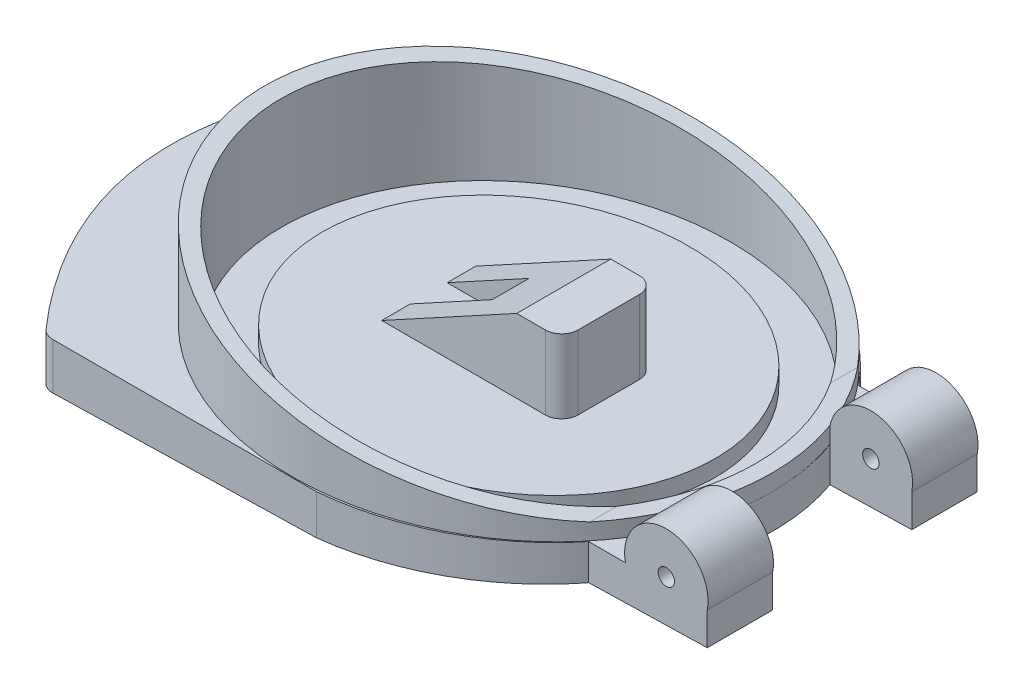
SolidWorks part; units mm, degrees
ref_plane "Front Plane" through (0, 0, 0) normal (0, 0, 1) x (1, 0, 0)
ref_plane "Top Plane" through (0, 0, 0) normal (0, 1, 0) x (1, 0, 0)
ref_plane "Right Plane" through (0, 0, 0) normal (1, 0, 0) x (0, 0, -1)
sketch "Sketch8" plane through (0, 0, 0) normal (0, 1, 0) x (1, 0, 0)
  line L0 (-55, 0) -> (55, 0) construction
  line L1 (29.5371, 8.5) -> (39.5371, 8.5)
  line L2 (3.1424, -27.8558) -> (-30, -27.8558)
  line L4 (3.1424, 27.8558) -> (-30, 27.8558)
  line L6 (21.6155, -20.0705) -> (-30, 27.8558) construction
  line L7 (21.6155, 20.0705) -> (-30, -27.8558) construction
  line L8 (29.5371, -8.5) -> (39.5371, -8.5)
  line L9 (39.5371, 8.5) -> (39.5371, 16.5)
  line L10 (39.5371, 16.5) -> (25.0457, 16.5)
  line L11 (39.5371, -8.5) -> (39.5371, -16.5)
  line L12 (39.5371, -16.5) -> (25.0457, -16.5)
  ellipse E0 centre (0, 0) end of major axis (31, 0) minor radius 28
  spline S0 degree 2 poles (-30, 27.8558) (-55, 0) (-30, -27.8558) knots 0 0 0 1 1 1
  dimension "D1" = 62
  dimension "D2" = 28
  dimension "D3" = 17
  dimension "D4" = 8.5
  dimension "D5" = 10
  dimension "D6" = 10
  dimension "D7" = 8
  dimension "D8" = 8
  dimension "D9" = 11.5
extrude "Boss-Extrude5" add sketch "Sketch8" along normal blind 4 contours L4 S0 L2 E0 | E0 L4 L2 | E0 L12 L11 L8 | E0 L1 L9 L10 region at (33.4938, 0, -12.749) region at (0, 0, 0) region at (33.4938, 0, 12.749) region at (-31.6821, 0, 0)
sketch "Sketch9" plane through (0, 4, 0) normal (0, 1, 0) x (1, 0, 0)
  line L0 (-11.457, 0) -> (11.457, 0) construction
  ellipse E0 centre (0, 0) end of major axis (31, 0) minor radius 27.7622
  ellipse E1 centre (0, 0) end of major axis (31, 0) minor radius 28 (29.5371, -8.5) -> (29.5371, 8.5) ccw construction
  ellipse E2 centre (0, 0) end of major axis (29, 0) minor radius 25.886
  dimension "D1" = 2
extrude "Boss-Extrude6" add sketch "Sketch9" along normal blind 12
sketch "Sketch10" plane through (0, 0, 27.8558) normal (0, 0, 1) x (1, 0, 0)
  line L0 (31, 6) -> (25.0457, 6)
  line L1 (31, 4) -> (31, 16) construction
  line L2 (39.5371, 4) -> (25.0457, 4) construction
  line L3 (25.0457, 6) -> (-31, 16)
  line L4 (-31, 16) -> (-31, 18.8124)
  line L5 (-31, 18.8124) -> (31, 18.8124)
  line L6 (31, 18.8124) -> (31, 6)
  dimension "D1" = 2
extrude "Cut-Extrude3" cut sketch "Sketch10" against normal blind 71
sketch "Sketch11" plane through (0, 0, 16.5) normal (0, 0, 1) x (1, 0, 0)
  line L0 (39.5371, 4) -> (39.5371, 5)
  line L1 (39.5371, 5) -> (34.5371, 5)
  line L2 (34.5371, 5) -> (34.5371, 0)
  line L3 (30.6413, 0) -> (-30.6413, 0) construction
  circle A1 centre (34.5371, 5) radius 1
  circle A2 centre (34.5371, 5) radius 5.099
  line M3 (25.0457, 0) -> (39.5371, 0)
  line M5 (39.5371, 4) -> (25.0457, 4)
  dimension "D1" = 5
  dimension "D2" = 5
extrude "Boss-Extrude8" add sketch "Sketch11" against normal up to surface (8 mm away) contours L0 A2 A1 L1 M5 | A1 L0 L1 M5 | A2 L2 M3 M5 | A2 L2 M5 M3 region at (37.4239, 4.4859, 16.5) region at (34.2581, 6.9603, 16.5) region at (36.5866, 2.2964, 16.5) region at (32.4875, 2.2964, 16.5) up to face at (34.5371, 2, 8.5)
sketch "Sketch12" plane through (0, 0, -16.5) normal (0, 0, -1) x (-1, 0, 0)
  line L0 (-34.5371, 4) -> (-34.5371, 5)
  line L1 (-39.5371, 4) -> (-25.0457, 4) construction
  circle A0 centre (-34.5371, 5) radius 1 construction
  circle A1 centre (-34.5371, 5) radius 1
  circle A2 centre (-34.5371, 5) radius 5.099
  line M1 (-39.5371, 0) -> (-25.0457, 0)
  line M3 (-25.0457, 4) -> (-39.5371, 4)
extrude "Boss-Extrude9" add sketch "Sketch12" against normal up to surface (8 mm away) contours A2 M3 M1 | A2 A1 M3 region at (34.5371, 6.7422, -16.5) region at (34.5371, 2.2964, -16.5) up to face at (34.5371, 2, -8.5)
sketch "Sketch14" plane through (0, 4, 0) normal (0, 1, 0) x (1, 0, 0)
  ellipse E3 centre (0, 0) end of major axis (29, 0) minor radius 25.886
  ellipse E4 centre (0, 0) end of major axis (29, 0) minor radius 25.886
  spline S0 degree 3 poles (-24, 0.3714) (-24, -1.4856) (-23.8193, -2.9396) (-23.3806, -4.72) (-23.2821, -5.0742) (-23.0635, -5.7788) (-22.943, -6.1303) (-22.552, -7.1701) (-22.2532, -7.8422) (-21.584, -9.147) (-21.2135, -9.7796) (-20.6056, -10.6997) (-20.3943, -11.0016) (-19.9542, -11.5958) (-19.7252, -11.8884) (-18.5496, -13.3125) (-17.5036, -14.3406) (-15.7909, -15.7312) (-15.193, -16.171) (-13.964, -16.9902) (-13.3343, -17.3692) (-11.4018, -18.419) (-10.0564, -19.0036) (-7.9549, -19.7126) (-7.2449, -19.9191) (-5.8195, -20.271) (-5.1021, -20.4171) (-2.9361, -20.7681) (-1.4729, -20.8864) (1.4872, -20.8856) (2.9474, -20.7667) (5.8294, -20.2988) (7.2511, -19.9499) (9.3526, -19.2411) (10.0422, -18.9754) (11.3858, -18.3907) (12.0419, -18.0709) (13.9629, -17.0283) (15.1807, -16.223) (16.6153, -15.0627) (16.8986, -14.8221) (17.45, -14.33) (17.7186, -14.0782) (18.5026, -13.306) (18.9967, -12.7684) (20.3912, -11.0865) (21.2052, -9.8737) (22.0573, -8.2267) (22.2187, -7.892) (22.5198, -7.2186) (22.6601, -6.879) (23.0504, -5.8515) (23.2698, -5.1549) (23.6258, -3.738) (23.7624, -3.0178) (23.9019, -1.9188) (23.9375, -1.5479) (23.9858, -0.8077) (23.9984, -0.4387) (24.0056, 1.4015) (23.8337, 2.8575) (23.3973, 4.6574) (23.2986, 5.0169) (23.0815, 5.7245) (22.9629, 6.0738) (22.5777, 7.1084) (22.282, 7.7805) (21.6154, 9.0909) (21.2443, 9.7293) (20.4282, 10.9715) (19.9897, 11.5651) (19.0562, 12.7015) (18.5612, 13.2442) (17.5168, 14.2806) (16.9664, 14.7752) (15.2409, 16.1809) (14.0172, 16.9952) (12.0825, 18.0506) (11.4208, 18.3744) (10.0645, 18.9667) (9.372, 19.2339) (7.2805, 19.9414) (5.8572, 20.2933) (3.6806, 20.6482) (2.947, 20.7375) (1.4697, 20.8567) (0.7334, 20.886) (-1.4683, 20.886) (-2.9269, 20.7694) (-5.1007, 20.4175) (-5.823, 20.2705) (-7.2625, 19.9145) (-7.9707, 19.7076) (-10.0554, 19.0033) (-11.3949, 18.4221) (-13.3251, 17.3745) (-13.9552, 16.9958) (-14.8791, 16.3804) (-15.1839, 16.167) (-15.7794, 15.7289) (-16.0709, 15.5037) (-17.4964, 14.347) (-18.5369, 13.3244) (-19.9367, 11.6339) (-20.3763, 11.0442) (-20.9916, 10.1167) (-21.189, 9.8007) (-21.5632, 9.1631) (-21.7407, 8.8406) (-22.5801, 7.2086) (-23.0999, 5.8426) (-23.6348, 3.6962) (-23.7721, 2.9606) (-23.9086, 1.855) (-23.9428, 1.4854) (-23.9885, 0.7443) (-24, 0.3714) (-24, -1.4856) (-23.8193, -2.9396) knots -0.007812 -0.007812 0 0 0.03125 0.03125 0.039063 0.039063 0.046875 0.046875 0.0625 0.0625 0.078125 0.078125 0.085938 0.085938 0.09375 0.09375 0.125 0.125 0.140625 0.140625 0.15625 0.15625 0.1875 0.1875 0.203125 0.203125 0.21875 0.21875 0.25 0.25 0.28125 0.28125 0.3125 0.3125 0.328125 0.328125 0.34375 0.34375 0.375 0.375 0.382813 0.382813 0.390625 0.390625 0.40625 0.40625 0.4375 0.4375 0.445313 0.445313 0.453125 0.453125 0.46875 0.46875 0.484375 0.484375 0.492188 0.492188 0.5 0.5 0.53125 0.53125 0.539063 0.539063 0.546875 0.546875 0.5625 0.5625 0.578125 0.578125 0.59375 0.59375 0.609375 0.609375 0.625 0.625 0.65625 0.65625 0.671875 0.671875 0.6875 0.6875 0.71875 0.71875 0.734375 0.734375 0.75 0.75 0.78125 0.78125 0.796875 0.796875 0.8125 0.8125 0.84375 0.84375 0.859375 0.859375 0.867188 0.867188 0.875 0.875 0.90625 0.90625 0.921875 0.921875 0.929688 0.929688 0.9375 0.9375 0.96875 0.96875 0.984375 0.984375 0.992188 0.992188 1 1 1.03125 1.03125 1.039062 only from (-24, 0) to (-24, 0)
  spline S1 degree 3 poles (-24, 0.3714) (-24, -1.4856) (-23.8193, -2.9396) (-23.3806, -4.72) (-23.2821, -5.0742) (-23.0635, -5.7788) (-22.943, -6.1303) (-22.552, -7.1701) (-22.2532, -7.8422) (-21.584, -9.147) (-21.2135, -9.7796) (-20.6056, -10.6997) (-20.3943, -11.0016) (-19.9542, -11.5958) (-19.7252, -11.8884) (-18.5496, -13.3125) (-17.5036, -14.3406) (-15.7909, -15.7312) (-15.193, -16.171) (-13.964, -16.9902) (-13.3343, -17.3692) (-11.4018, -18.419) (-10.0564, -19.0036) (-7.9549, -19.7126) (-7.2449, -19.9191) (-5.8195, -20.271) (-5.1021, -20.4171) (-2.9361, -20.7681) (-1.4729, -20.8864) (1.4872, -20.8856) (2.9474, -20.7667) (5.8294, -20.2988) (7.2511, -19.9499) (9.3526, -19.2411) (10.0422, -18.9754) (11.3858, -18.3907) (12.0419, -18.0709) (13.9629, -17.0283) (15.1807, -16.223) (16.6153, -15.0627) (16.8986, -14.8221) (17.45, -14.33) (17.7186, -14.0782) (18.5026, -13.306) (18.9967, -12.7684) (20.3912, -11.0865) (21.2052, -9.8737) (22.0573, -8.2267) (22.2187, -7.892) (22.5198, -7.2186) (22.6601, -6.879) (23.0504, -5.8515) (23.2698, -5.1549) (23.6258, -3.738) (23.7624, -3.0178) (23.9019, -1.9188) (23.9375, -1.5479) (23.9858, -0.8077) (23.9984, -0.4387) (24.0056, 1.4015) (23.8337, 2.8575) (23.3973, 4.6574) (23.2986, 5.0169) (23.0815, 5.7245) (22.9629, 6.0738) (22.5777, 7.1084) (22.282, 7.7805) (21.6154, 9.0909) (21.2443, 9.7293) (20.4282, 10.9715) (19.9897, 11.5651) (19.0562, 12.7015) (18.5612, 13.2442) (17.5168, 14.2806) (16.9664, 14.7752) (15.2409, 16.1809) (14.0172, 16.9952) (12.0825, 18.0506) (11.4208, 18.3744) (10.0645, 18.9667) (9.372, 19.2339) (7.2805, 19.9414) (5.8572, 20.2933) (3.6806, 20.6482) (2.947, 20.7375) (1.4697, 20.8567) (0.7334, 20.886) (-1.4683, 20.886) (-2.9269, 20.7694) (-5.1007, 20.4175) (-5.823, 20.2705) (-7.2625, 19.9145) (-7.9707, 19.7076) (-10.0554, 19.0033) (-11.3949, 18.4221) (-13.3251, 17.3745) (-13.9552, 16.9958) (-14.8791, 16.3804) (-15.1839, 16.167) (-15.7794, 15.7289) (-16.0709, 15.5037) (-17.4964, 14.347) (-18.5369, 13.3244) (-19.9367, 11.6339) (-20.3763, 11.0442) (-20.9916, 10.1167) (-21.189, 9.8007) (-21.5632, 9.1631) (-21.7407, 8.8406) (-22.5801, 7.2086) (-23.0999, 5.8426) (-23.6348, 3.6962) (-23.7721, 2.9606) (-23.9086, 1.855) (-23.9428, 1.4854) (-23.9885, 0.7443) (-24, 0.3714) (-24, -1.4856) (-23.8193, -2.9396) knots -0.007812 -0.007812 0 0 0.03125 0.03125 0.039063 0.039063 0.046875 0.046875 0.0625 0.0625 0.078125 0.078125 0.085938 0.085938 0.09375 0.09375 0.125 0.125 0.140625 0.140625 0.15625 0.15625 0.1875 0.1875 0.203125 0.203125 0.21875 0.21875 0.25 0.25 0.28125 0.28125 0.3125 0.3125 0.328125 0.328125 0.34375 0.34375 0.375 0.375 0.382813 0.382813 0.390625 0.390625 0.40625 0.40625 0.4375 0.4375 0.445313 0.445313 0.453125 0.453125 0.46875 0.46875 0.484375 0.484375 0.492188 0.492188 0.5 0.5 0.53125 0.53125 0.539063 0.539063 0.546875 0.546875 0.5625 0.5625 0.578125 0.578125 0.59375 0.59375 0.609375 0.609375 0.625 0.625 0.65625 0.65625 0.671875 0.671875 0.6875 0.6875 0.71875 0.71875 0.734375 0.734375 0.75 0.75 0.78125 0.78125 0.796875 0.796875 0.8125 0.8125 0.84375 0.84375 0.859375 0.859375 0.867188 0.867188 0.875 0.875 0.90625 0.90625 0.921875 0.921875 0.929688 0.929688 0.9375 0.9375 0.96875 0.96875 0.984375 0.984375 0.992188 0.992188 1 1 1.03125 1.03125 1.039062 only from (-24, 0) to (-24, 0)
  ellipse M3 centre (0, 0) end of major axis (29, 0) minor radius 25.886
  dimension "D1" = 5
  dimension "D2" = 0
extrude "Cut-Extrude4" cut sketch "Sketch14" against normal blind 2 contours S1 M3 region at (-28.2225, 4, 0.0005)
sketch "Sketch15" plane through (0, 4, 0) normal (0, 1, 0) x (1, 0, 0)
  line L0 (24, 0) -> (11, 0)
  line L1 (-9.3239, 0) -> (9.3239, 0) construction
  line L2 (11, 0) -> (11, 5.75)
  line L3 (11, 5.75) -> (-11, 5.75)
  line L4 (-11, 5.75) -> (-11, 2.25)
  line L5 (-11, -5.75) -> (11, -5.75)
  line L6 (11, -5.75) -> (11, 0)
  line L7 (-11, 2.25) -> (-1, 2.25)
  line L8 (-1, 2.25) -> (-1, -2.25)
  line L9 (-1, -2.25) -> (-11, -2.25)
  line L10 (-11, -2.25) -> (-11, -5.75)
  spline S0 degree 3 poles (-24, 0) (-24, -1.4856) (-23.8193, -2.9396) (-23.3806, -4.72) (-23.2821, -5.0742) (-23.0635, -5.7788) (-22.943, -6.1303) (-22.552, -7.1701) (-22.2532, -7.8422) (-21.584, -9.147) (-21.2135, -9.7796) (-20.6056, -10.6997) (-20.3943, -11.0016) (-19.9542, -11.5958) (-19.7252, -11.8884) (-18.5496, -13.3125) (-17.5036, -14.3406) (-15.7909, -15.7312) (-15.193, -16.171) (-13.964, -16.9902) (-13.3343, -17.3692) (-11.4018, -18.419) (-10.0564, -19.0036) (-7.9549, -19.7126) (-7.2449, -19.9191) (-5.8195, -20.271) (-5.1021, -20.4171) (-2.9361, -20.7681) (-1.4729, -20.8864) (1.4872, -20.8856) (2.9474, -20.7667) (5.8294, -20.2988) (7.2511, -19.9499) (9.3526, -19.2411) (10.0422, -18.9754) (11.3858, -18.3907) (12.0419, -18.0709) (13.9629, -17.0283) (15.1807, -16.223) (16.6153, -15.0627) (16.8986, -14.8221) (17.45, -14.33) (17.7186, -14.0782) (18.5026, -13.306) (18.9967, -12.7684) (20.3912, -11.0865) (21.2052, -9.8737) (22.0573, -8.2267) (22.2187, -7.892) (22.5198, -7.2186) (22.6601, -6.879) (23.0504, -5.8515) (23.2698, -5.1549) (23.6258, -3.738) (23.7624, -3.0178) (23.9019, -1.9188) (23.9375, -1.5479) (23.9858, -0.8077) (23.9984, -0.4387) (24.0056, 1.4015) (23.8337, 2.8575) (23.3973, 4.6574) (23.2986, 5.0169) (23.0815, 5.7245) (22.9629, 6.0738) (22.5777, 7.1084) (22.282, 7.7805) (21.6154, 9.0909) (21.2443, 9.7293) (20.4282, 10.9715) (19.9897, 11.5651) (19.0562, 12.7015) (18.5612, 13.2442) (17.5168, 14.2806) (16.9664, 14.7752) (15.2409, 16.1809) (14.0172, 16.9952) (12.0825, 18.0506) (11.4208, 18.3744) (10.0645, 18.9667) (9.372, 19.2339) (7.2805, 19.9414) (5.8572, 20.2933) (3.6806, 20.6482) (2.947, 20.7375) (1.4697, 20.8567) (0.7334, 20.886) (-1.4683, 20.886) (-2.9269, 20.7694) (-5.1007, 20.4175) (-5.823, 20.2705) (-7.2625, 19.9145) (-7.9707, 19.7076) (-10.0554, 19.0033) (-11.3949, 18.4221) (-13.3251, 17.3745) (-13.9552, 16.9958) (-14.8791, 16.3804) (-15.1839, 16.167) (-15.7794, 15.7289) (-16.0709, 15.5037) (-17.4964, 14.347) (-18.5369, 13.3244) (-19.9367, 11.6339) (-20.3763, 11.0442) (-20.9916, 10.1167) (-21.189, 9.8007) (-21.5632, 9.1631) (-21.7407, 8.8406) (-22.5801, 7.2086) (-23.0999, 5.8426) (-23.6348, 3.6962) (-23.7721, 2.9606) (-23.9086, 1.855) (-23.9428, 1.4854) (-23.9885, 0.7443) (-24, 0.3714) (-24, 0) (-24, -1.4856) (-23.8193, -2.9396) knots -0.007812 0 0 0 0.03125 0.03125 0.039063 0.039063 0.046875 0.046875 0.0625 0.0625 0.078125 0.078125 0.085938 0.085938 0.09375 0.09375 0.125 0.125 0.140625 0.140625 0.15625 0.15625 0.1875 0.1875 0.203125 0.203125 0.21875 0.21875 0.25 0.25 0.28125 0.28125 0.3125 0.3125 0.328125 0.328125 0.34375 0.34375 0.375 0.375 0.382813 0.382813 0.390625 0.390625 0.40625 0.40625 0.4375 0.4375 0.445313 0.445313 0.453125 0.453125 0.46875 0.46875 0.484375 0.484375 0.492188 0.492188 0.5 0.5 0.53125 0.53125 0.539063 0.539063 0.546875 0.546875 0.5625 0.5625 0.578125 0.578125 0.59375 0.59375 0.609375 0.609375 0.625 0.625 0.65625 0.65625 0.671875 0.671875 0.6875 0.6875 0.71875 0.71875 0.734375 0.734375 0.75 0.75 0.78125 0.78125 0.796875 0.796875 0.8125 0.8125 0.84375 0.84375 0.859375 0.859375 0.867188 0.867188 0.875 0.875 0.90625 0.90625 0.921875 0.921875 0.929688 0.929688 0.9375 0.9375 0.96875 0.96875 0.984375 0.984375 0.992188 0.992188 1 1 1 1.03125 1.03125 1.039062 only from (-24, 0) to (-24, 0) construction
  dimension "D1" = 13
  dimension "D2" = 11.5
  dimension "D3" = 5.75
  dimension "D4" = 22
  dimension "D5" = 3.5
  dimension "D6" = 3.5
  dimension "D7" = 10
extrude "Boss-Extrude10" add sketch "Sketch15" along normal blind 9 contours L9 L10 L5 L6 L2 L3 L4 L7 L8 region at (1.2981, 4, 0)
sketch "Sketch16" plane through (0, 0, 5.75) normal (0, 0, 1) x (1, 0, 0)
  line L0 (11, 13) -> (5.5, 13)
  line L1 (-11, 13) -> (11, 13) construction
  line L2 (5.5, 13) -> (-11, 4)
  line L3 (-11, 4) -> (-11, 16.4689)
  line L4 (-11, 16.4689) -> (5.5, 16.4689)
  line L5 (5.5, 16.4689) -> (5.5, 13)
  line M4 (11, 13) -> (-11, 13)
  line M5 (-11, 13) -> (-11, 4)
  dimension "D1" = 5.5
extrude "Cut-Extrude5" cut sketch "Sketch16" against normal blind 13 contours L5 L4 L3 M4 | L2 M4 M5 region at (-2.75, 14.7344, 5.75) region at (-5.5, 10, 5.75)
fillet "Fillet1" radius 2 4 edges at (-30, 2, -27.8558) (-30, 2, 27.8558) (11, 8.5, -5.75) (11, 8.5, 5.75)
sketch "Sketch17" plane through (0, 0, 0) normal (0, -1, 0) x (1, 0, 0)
  line L16 (-29.1003, -27.8558) -> (3.1424, -27.8558)
  line L17 (25.0457, -16.5) -> (39.5371, -16.5)
  line L18 (39.5371, -16.5) -> (39.5371, -8.5)
  line L19 (39.5371, -8.5) -> (29.5371, -8.5)
  line L20 (29.5371, 8.5) -> (39.5371, 8.5)
  line L21 (39.5371, 8.5) -> (39.5371, 16.5)
  line L22 (39.5371, 16.5) -> (25.0457, 16.5)
  line L23 (3.1424, 27.8558) -> (-29.1003, 27.8558)
  line L24 (-29.1003, -27.8558) -> (3.1424, -27.8558)
  line L25 (25.0457, -16.5) -> (39.5371, -16.5)
  line L26 (39.5371, -16.5) -> (39.5371, -8.5)
  line L27 (39.5371, -8.5) -> (29.5371, -8.5)
  line L28 (29.5371, 8.5) -> (39.5371, 8.5)
  line L29 (39.5371, 8.5) -> (39.5371, 16.5)
  line L30 (39.5371, 16.5) -> (25.0457, 16.5)
  line L31 (3.1424, 27.8558) -> (-29.1003, 27.8558)
  arc A4 (-30.6051, -27.1732) -> (-29.1003, -27.8558) centre (-29.1003, -25.8558) ccw
  arc A5 (-29.1003, 27.8558) -> (-30.6051, 27.1732) centre (-29.1003, 25.8558) ccw
  arc A6 (-30.6051, -27.1732) -> (-29.1003, -27.8558) centre (-29.1003, -25.8558) ccw
  arc A7 (-29.1003, 27.8558) -> (-30.6051, 27.1732) centre (-29.1003, 25.8558) ccw
  ellipse E6 centre (0, 0) end of major axis (31, 0) minor radius 28 (3.1424, -27.8558) -> (25.0457, -16.5) ccw
  ellipse E7 centre (0, 0) end of major axis (31, 0) minor radius 28 (29.5371, -8.5) -> (29.5371, 8.5) ccw
  ellipse E8 centre (0, 0) end of major axis (31, 0) minor radius 28 (25.0457, 16.5) -> (3.1424, 27.8558) ccw
  ellipse E9 centre (0, 0) end of major axis (31, 0) minor radius 28 (3.1424, -27.8558) -> (25.0457, -16.5) ccw
  ellipse E10 centre (0, 0) end of major axis (31, 0) minor radius 28 (29.5371, -8.5) -> (29.5371, 8.5) ccw
  ellipse E11 centre (0, 0) end of major axis (31, 0) minor radius 28 (25.0457, 16.5) -> (3.1424, 27.8558) ccw
  parabola Q2 (-30.6051, 27.1732) -> (-30.6051, -27.1732) focus (-26.9811, 0) apex (-42.5, 0)
  parabola Q3 (-30.6051, 27.1732) -> (-30.6051, -27.1732) focus (-26.9811, 0) apex (-42.5, 0)
  dimension "D1" = 0
extrude "Boss-Extrude11" add sketch "Sketch17" along normal blind 2
sketch "Sketch18" plane through (0, 0, 27.8558) normal (0, 0, 1) x (1, 0, 0)
  line L0 (-42.5, -2) -> (39.5371, 0)
  line L1 (31.3275, 0) -> (-31.3275, 0) construction
  line L2 (39.5371, 4) -> (39.5371, -2) construction
  line L3 (39.5371, 0) -> (39.5371, -5.5881)
  line L4 (39.5371, -5.5881) -> (-42.5, -7.1738)
  line L5 (-42.5, -7.1738) -> (-42.5, -2)
extrude "Cut-Extrude6" cut sketch "Sketch18" against normal blind 80
